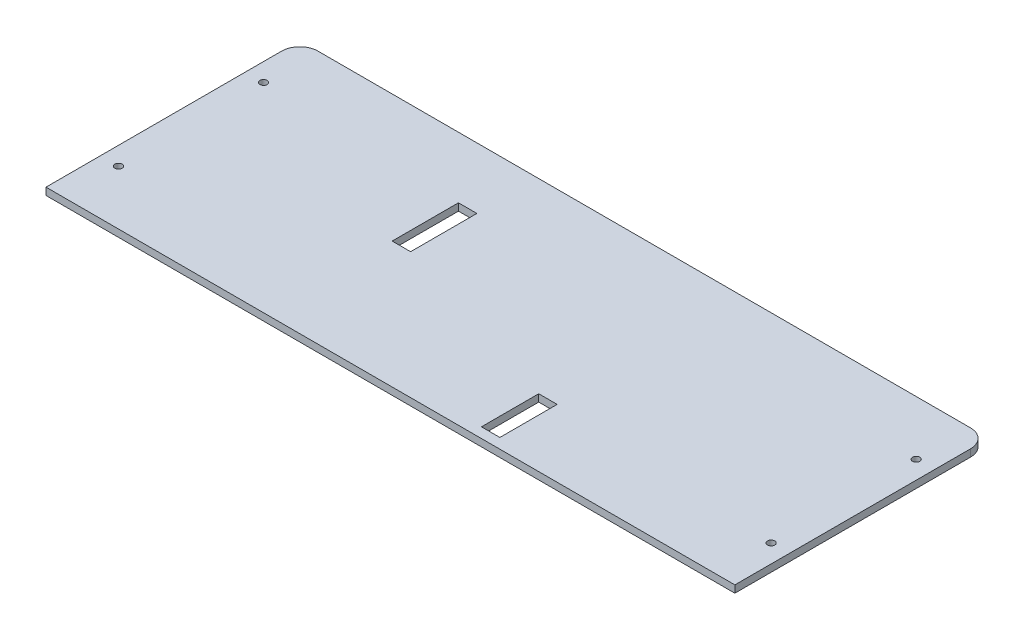
SolidWorks part; units mm, degrees
material "Калифорния"
ref_plane "Спереди" through (0, 0, 0) normal (0, 0, 1) x (1, 0, 0)
ref_plane "Сверху" through (0, 0, 0) normal (0, 1, 0) x (1, 0, 0)
ref_plane "Справа" through (0, 0, 0) normal (1, 0, 0) x (0, 0, -1)
sketch "Эскиз1" plane through (0, 0, 0) normal (0, 1, 0) x (1, 0, 0)
  line L0 (0, 56.6874) -> (0, -54.7718) construction
  line L1 (90, 35) -> (-90, 35)
  line L2 (95, 30) -> (95, -35)
  line L3 (95, -35) -> (-95, -35)
  line L4 (-95, 30) -> (-95, -35)
  line L5 (95, 35) -> (-95, -35) construction
  line L6 (95, -35) -> (-95, 35) construction
  line L7 (-34.38, -0.14) -> (-29.3, 18.14) construction
  line L8 (22.3, -32.2) -> (27.38, -32.2)
  line L9 (22.3, -32.2) -> (22.3, -16.4)
  line L10 (22.3, -16.4) -> (27.38, -16.4)
  line L11 (27.38, -32.2) -> (27.38, -16.4)
  line L12 (-34.38, -0.14) -> (-29.3, -0.14)
  line L13 (-34.38, -0.14) -> (-34.38, 18.14)
  line L14 (-34.38, 18.14) -> (-29.3, 18.14)
  line L15 (-29.3, -0.14) -> (-29.3, 18.14)
  line L16 (-34.38, 18.14) -> (-29.3, -0.14) construction
  line L17 (22.3, -16.4) -> (27.38, -32.2) construction
  line L18 (22.3, -32.2) -> (27.38, -16.4) construction
  arc A0 (90, 35) -> (95, 30) centre (90, 30) cw
  arc A1 (-90, 35) -> (-95, 30) centre (-90, 30) ccw
  circle A2 centre (-90, 20) radius 1
  circle A3 centre (-90, -20) radius 1
  circle A4 centre (90, -20) radius 1
  circle A5 centre (90, 20) radius 1
  point P0 (0, 0)
  dimension "D3" = 5
  dimension "D4" = 15
  dimension "D6" = 2
  dimension "D1" = 70
  dimension "D2" = 190
  dimension "D5" = 5
  dimension "D8" = 15
  dimension "D9" = 5.08
  dimension "D10" = 15.8
  dimension "D11" = 22.3
  dimension "D12" = 2.8
  dimension "D13" = 5.08
  dimension "D14" = 18.28
  dimension "D15" = 29.3
  dimension "D16" = 16.86
  dimension "D7" = 2
extrude "Сейвер" add sketch "Эскиз1" along normal blind 2
sketch "Эскиз2" plane through (0, 0, 0) normal (0, 1, 0) x (1, 0, 0)
  line L0 (-34.38, 18.14) -> (-34.38, -0.14) construction
  line L1 (90, 35) -> (-90, 35) construction
  line L2 (95, -35) -> (95, 30) construction
  circle A0 centre (30, 5) radius 5
  circle A1 centre (-49.38, 5) radius 5
  dimension "D1" = 10
  dimension "D2" = 10
  dimension "D3" = 15
  dimension "D4" = 30
  dimension "D5" = 30
  dimension "D6" = 65
extrude "Держатели экранов" add sketch "Эскиз2" against normal blind 14.5
fillet "Скругление1" radius 2 2 edges at (-49.38, 0, -10) (30, 0, -10) conic radius 10
